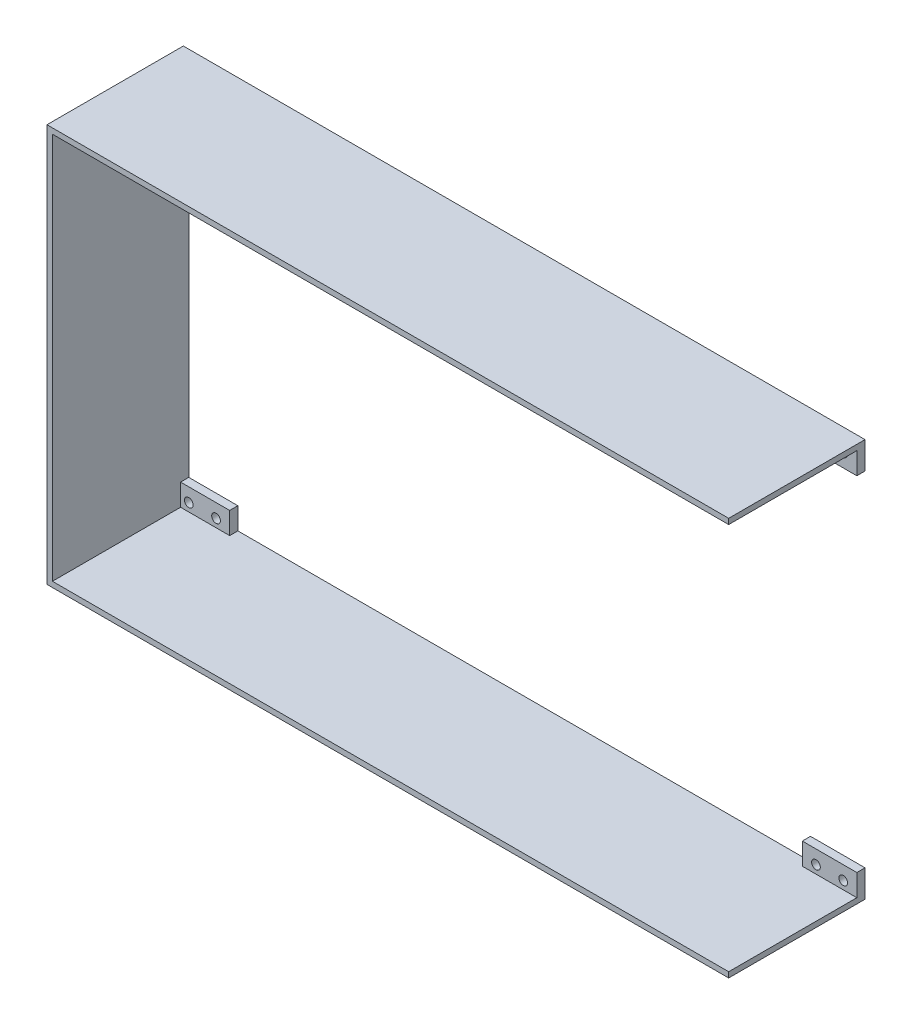
SolidWorks part; units mm, degrees
material "Thornel Mat VMA"
ref_plane "前视基准面" through (0, 0, 0) normal (0, 0, 1) x (1, 0, 0)
ref_plane "上视基准面" through (0, 0, 0) normal (0, 1, 0) x (1, 0, 0)
ref_plane "右视基准面" through (0, 0, 0) normal (1, 0, 0) x (0, 0, -1)
other "Configuration Table"
sketch "草图1" plane through (0, 0, 0) normal (0, 0, 1) x (1, 0, 0)
  line L0 (-146.1797, -43.9555) -> (-136.1797, -43.9555) construction
  line L1 (-151.1797, 97.0445) -> (98.8203, 97.0445)
  line L2 (-151.1797, 97.0445) -> (-151.1797, -48.9555)
  line L3 (-151.1797, -48.9555) -> (98.8203, -48.9555)
  line L4 (98.8203, 97.0445) -> (98.8203, 95.0445)
  line L5 (-151.1797, 24.0445) -> (98.8203, 24.0445) construction
  line L6 (-149.1797, 95.0445) -> (96.8203, 95.0445)
  line L8 (-149.1797, -46.9555) -> (96.8203, -46.9555)
  line L9 (-149.1797, 95.0445) -> (-149.1797, -46.9555)
  line L10 (96.8203, 95.0445) -> (98.8203, 95.0445)
  line L11 (96.8203, -46.9555) -> (98.8203, -46.9555)
  line L12 (96.8203, 95.0445) -> (96.8203, -46.9555) construction
  line L13 (98.8203, -46.9555) -> (98.8203, -48.9555)
  line L14 (98.8203, 97.0445) -> (98.8203, -48.9555) construction
  circle A0 centre (-146.1797, -43.9555) radius 1.6 construction
  circle A1 centre (-136.1797, -43.9555) radius 1.6 construction
  circle A2 centre (-146.1797, 92.0445) radius 1.6 construction
  circle A3 centre (-136.1797, 92.0445) radius 1.6 construction
  circle A4 centre (93.8203, -43.9555) radius 1.5703 construction
  circle A5 centre (83.8203, -43.9555) radius 1.5703 construction
  circle A6 centre (93.8203, 92.0445) radius 1.5703 construction
  circle A7 centre (83.8203, 92.0445) radius 1.5703 construction
  dimension "D6" = 3.2
  dimension "D1" = 250
  dimension "D2" = 146
  dimension "D3" = 10
  dimension "D4" = 5
  dimension "D5" = 5
  dimension "D7" = 10
  dimension "D8" = 5
  dimension "D9" = 5
  dimension "D10" = 2
extrude "凸台-拉伸1" add sketch "草图1" along normal blind 50
sketch "草图2" plane through (0, 0, 0) normal (0, 0, 1) x (1, 0, 0)
  line L0 (-26.1797, -46.9555) -> (-26.1797, 95.0445) construction
  line L1 (-151.1797, -48.9555) -> (-131.1797, -48.9555)
  line L2 (-151.1797, -48.9555) -> (-151.1797, -38.9555)
  line L3 (-151.1797, -38.9555) -> (-131.1797, -38.9555)
  line L4 (-131.1797, -48.9555) -> (-131.1797, -38.9555)
  line L5 (-149.1797, -46.9555) -> (96.8203, -46.9555) construction
  line L6 (-149.1797, 95.0445) -> (96.8203, 95.0445) construction
  line L7 (-151.1797, 24.0445) -> (-26.1797, 24.0445) construction
  line L8 (-151.1797, 24.0445) -> (98.8203, 24.0445) construction
  line L9 (78.8203, -48.9555) -> (78.8203, -38.9555)
  line L10 (98.8203, -38.9555) -> (78.8203, -38.9555)
  line L11 (98.8203, -48.9555) -> (98.8203, -38.9555)
  line L12 (98.8203, -48.9555) -> (78.8203, -48.9555)
  line L13 (98.8203, 97.0445) -> (78.8203, 97.0445)
  line L14 (98.8203, 97.0445) -> (98.8203, 87.0445)
  line L15 (98.8203, 87.0445) -> (78.8203, 87.0445)
  line L16 (78.8203, 97.0445) -> (78.8203, 87.0445)
  line L17 (-131.1797, 97.0445) -> (-131.1797, 87.0445)
  line L18 (-151.1797, 87.0445) -> (-131.1797, 87.0445)
  line L19 (-151.1797, 97.0445) -> (-151.1797, 87.0445)
  line L20 (-151.1797, 97.0445) -> (-131.1797, 97.0445)
  circle A0 centre (-146.1797, -43.9555) radius 1.6
  circle A1 centre (-136.1797, -43.9555) radius 1.6
  circle A2 centre (83.8203, -43.9555) radius 1.6
  circle A3 centre (93.8203, -43.9555) radius 1.6
  circle A4 centre (93.8203, 92.0445) radius 1.6
  circle A5 centre (83.8203, 92.0445) radius 1.6
  circle A6 centre (-136.1797, 92.0445) radius 1.6
  circle A7 centre (-146.1797, 92.0445) radius 1.6
  dimension "D3" = 3.2
  dimension "D1" = 20
  dimension "D2" = 10
extrude "凸台-拉伸2" add sketch "草图2" along normal blind 3
